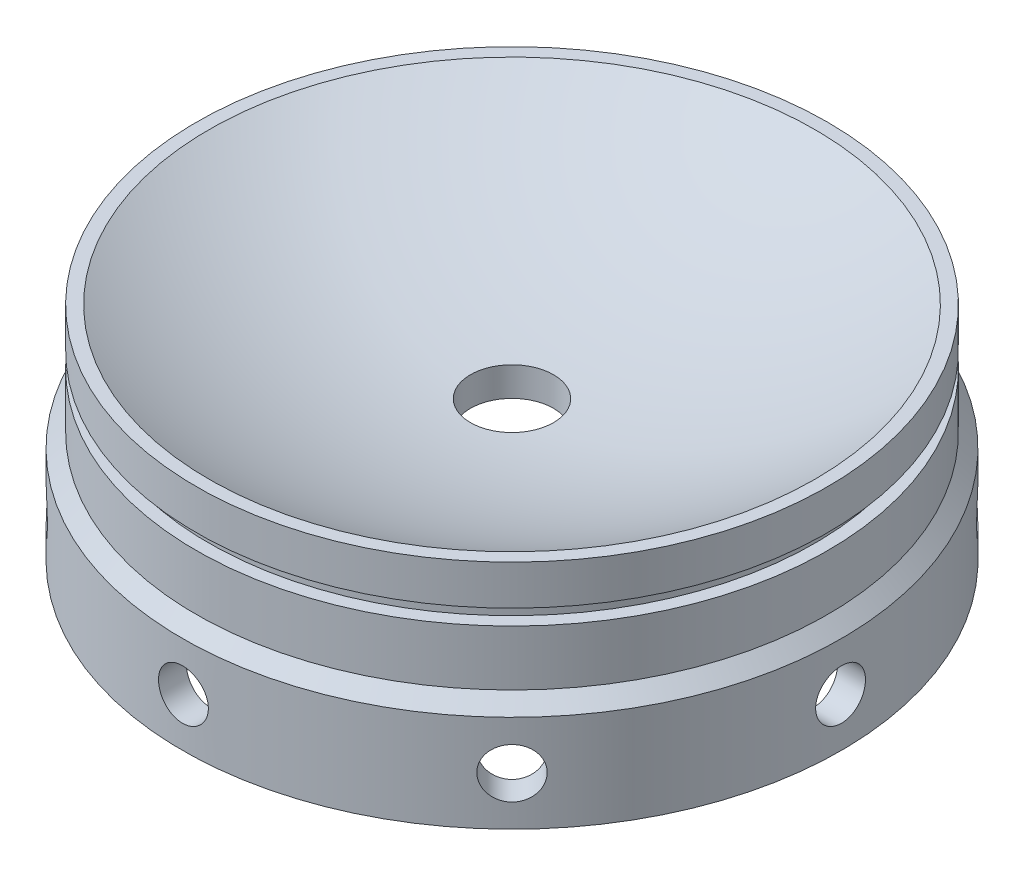
SolidWorks part; units mm, degrees
ref_plane "Front Plane" through (0, 0, 0) normal (0, 0, 1) x (1, 0, 0)
ref_plane "Top Plane" through (0, 0, 0) normal (0, 1, 0) x (1, 0, 0)
ref_plane "Right Plane" through (0, 0, 0) normal (1, 0, 0) x (0, 0, -1)
sketch "Sketch1" plane through (0, 0, 0) normal (0, 0, 1) x (1, 0, 0)
  line L0 (0, 0) -> (0, 6.35)
  line L1 (0, 0) -> (72.39, 0)
  line L2 (72.39, 0) -> (72.39, 12.7)
  line L3 (72.39, 12.7) -> (69.469, 12.7)
  line L4 (69.469, 12.7) -> (69.469, 16.256)
  line L5 (69.469, 16.256) -> (72.39, 16.256)
  line L6 (72.39, 16.256) -> (72.39, 25.4)
  line L7 (72.39, 25.4) -> (69.469, 25.4)
  line L8 (69.469, 25.4) -> (69.469, 6.35) construction
  line L9 (69.469, 6.35) -> (0, 6.35) construction
  line L10 (69.215, -25.4) -> (75.565, -25.4)
  line L11 (72.39, 0) -> (75.565, -3.175)
  line L12 (75.565, -25.4) -> (75.565, 0)
  line L13 (75.565, 0) -> (72.39, 0)
  line L14 (69.215, -25.4) -> (69.215, 0)
  line L15 (66.04, 0) -> (69.215, -3.175)
  line L16 (9.525, 6.6835) -> (9.525, 0)
  line L17 (73.025, 45.3691) -> (73.025, 21.7883) construction
  arc A0 (69.469, 25.4) -> (0, 6.35) centre (0, 142.5401) cw
  point P21 (0, 0)
  dimension "D1" = 72.39
  dimension "D7" = 6.35
  dimension "D6" = 75.565
  dimension "D8" = 25.4
  dimension "D5" = 25.4
  dimension "D9" = 6.35
  dimension "D10" = 45
  dimension "D11" = 45
  dimension "D12" = 9.525
  dimension "D3" = 12.7
  dimension "D4" = 3.556
  dimension "D2" = 73.025
  dimension "D13" = 3.556
revolve "Revolve1" add sketch "Sketch1" angle 360 about L0 region at (48.1528, 8.1766, 0) region at (68.1567, -1.0583, 0) region at (72.3217, -13.0755, 0)
hole_wizard "1/2 (0.45) Diameter Hole1" positions "3DSketch5" profile "Sketch8" hole size "1/2" standard "ANSI Inch"
sketch3d "3DSketch5"
  line L0 (0, -25.4, 0) -> (0, -3.175, 0) construction
  line L2 (0, -14.2875, 0) -> (75.565, -14.2875, 0)
  circle A2 centre (0, -25.4, 0) radius 75.565 construction
  circle A3 centre (0, -25.4, 0) radius 75.565
  circle A6 centre (0, -3.175, 0) radius 75.565 construction
  circle A7 centre (0, -3.175, 0) radius 75.565
  point P0 (75.565, -14.2875, 0)
  point P10 (0, -100.965, 0)
  point P12 (0, -100.965, 0)
  point P26 (0, -78.74, 0)
  point P28 (0, -78.74, 0)
sketch "Sketch8" plane through (75.565, -14.2875, 0) normal (0, 1, 0) x (0, 0, -1)
  line L0 (0, 0) -> (0, 78.9979)
  line L1 (0, 78.9979) -> (5.715, 75.564)
  line L2 (5.715, 75.564) -> (5.715, 0)
  line L5 (5.715, 0) -> (0, 0)
  line L10 (0, 78.9979) -> (-5.715, 75.564) construction
  line L11 (0, -6.35) -> (0, 107.95) construction
  dimension "Hole Dia." = 11.43
  dimension "Hole Depth" = 75.564
  dimension "Drill Angle" = 118
pattern_circular "CirPattern1" count 8 over 360 about axis through (0, -25.4, 0) along (0, -1, 0) of "1/2 (0.45) Diameter Hole1"
ref_axis "CenterAxis" through (0, 6.6835, 0) along (0, -1, 0)
equation "\"D1@Sketch1\"=(5.75/2)-(0.025in)"
equation "\"D6@Sketch1\"=5.95/2"
equation "\"D12@Sketch1\"=0.75/2"
equation "\"D2@Sketch1\"=5.75/2"
